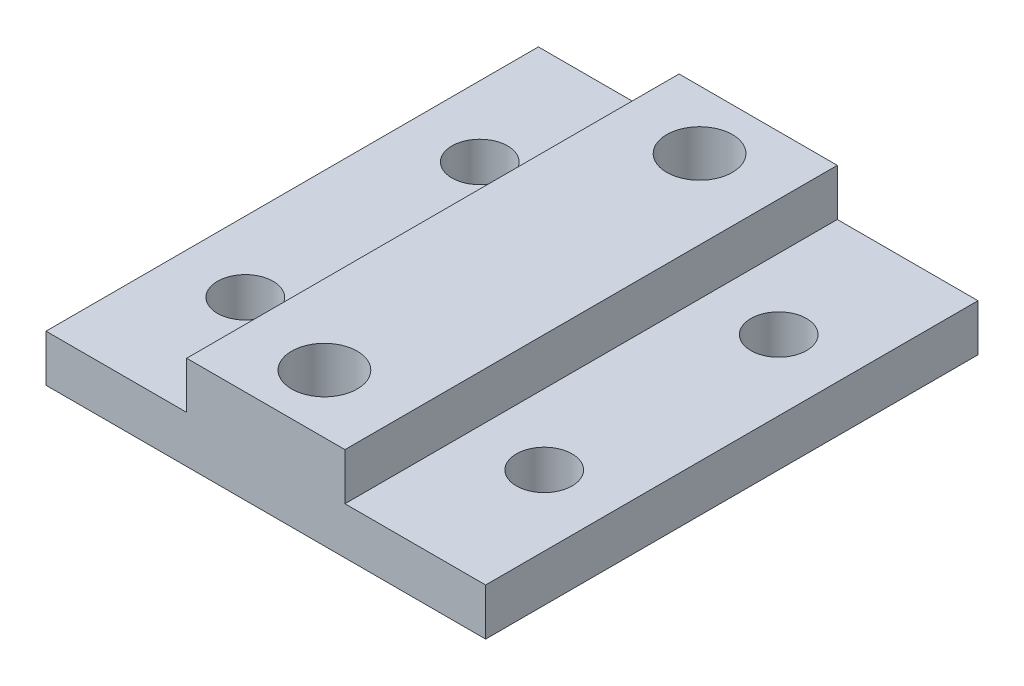
SolidWorks part; units mm, degrees
note: The reader was unsure of these and kept them because the rebuilt part matched: shared geometry of "Esboço1<3>".
ref_plane "Plano frontal" through (0, 0, 0) normal (0, 0, 1) x (1, 0, 0)
ref_plane "Plano superior" through (0, 0, 0) normal (0, 1, 0) x (1, 0, 0)
ref_plane "Plano direito" through (0, 0, 0) normal (1, 0, 0) x (0, 0, -1)
sketch "Esboço1" plane through (0, 0, 0) normal (0, 1, 0) x (1, 0, 0)
  line L1 (-18.75, 21) -> (18.75, 21)
  line L2 (-18.75, 21) -> (-18.75, -21)
  line L3 (-18.75, -21) -> (18.75, -21)
  line L4 (18.75, 21) -> (18.75, -21)
  line L5 (-18.75, 21) -> (18.75, -21) construction
  line L6 (-18.75, -21) -> (18.75, 21) construction
  line L7 (-6.75, -21) -> (6.75, -21)
  line L8 (-6.75, -21) -> (-6.75, 21)
  line L9 (-6.75, 21) -> (6.75, 21)
  line L10 (6.75, -21) -> (6.75, 21)
  line L11 (-6.75, -21) -> (6.75, 21) construction
  line L12 (-6.75, 21) -> (6.75, -21) construction
  circle A0 centre (0, 16) radius 2.8
  circle A1 centre (0, -16) radius 2.8
  circle A2 centre (12.75, 10) radius 2.375
  circle A3 centre (12.75, -10) radius 2.375
  circle A4 centre (-12.75, 10) radius 2.375
  circle A5 centre (-12.75, -10) radius 2.375
  point P0 (0, 0)
  point P18 (0, 0)
  dimension "D1" = 5.6
  dimension "D2" = 5.6
  dimension "D3" = 4.75
  dimension "D4" = 4.75
  dimension "D5" = 4.75
  dimension "D6" = 4.75
  dimension "D7" = 11
  dimension "D8" = 11
  dimension "D9" = 11
  dimension "D11" = 6
  dimension "D12" = 6
  dimension "D13" = 6
  dimension "D14" = 6
  dimension "D16" = 42
  dimension "D17" = 32
  dimension "D18" = 16
  dimension "D10" = 20
  dimension "D19" = 13.5
  dimension "D15" = 6
extrude "Ressalto-extrusão1" add sketch "Esboço1" along normal blind 5 contours L3 L8 L1 L2 A5 A4 | L3 L10 L1 L8 A1 A0 | L10 L3 L4 L1 A3 A2
sketch "Esboço2" plane through (0, 5, 0) normal (0, 1, 0) x (1, 0, 0)
  line L1 (5.0229, 16) -> (2.5115, 20.35)
  line L2 (2.5115, 20.35) -> (-2.5115, 20.35)
  line L3 (-2.5115, 20.35) -> (-5.0229, 16)
  line L4 (-5.0229, 16) -> (-2.5115, 11.65)
  line L5 (-2.5115, 11.65) -> (2.5115, 11.65)
  line L6 (2.5115, 11.65) -> (5.0229, 16)
  line L7 (5.0229, -16) -> (2.5115, -11.65)
  line L8 (2.5115, -11.65) -> (-2.5115, -11.65)
  line L9 (-2.5115, -11.65) -> (-5.0229, -16)
  line L10 (-5.0229, -16) -> (-2.5115, -20.35)
  line L11 (-2.5115, -20.35) -> (2.5115, -20.35)
  line L12 (2.5115, -20.35) -> (5.0229, -16)
  circle A0 centre (0, 16) radius 4.35 construction
  circle A1 centre (0, -16) radius 4.35 construction
  dimension "D1" = 8.7
  dimension "D2" = 8.7
extrude "Corte-extrusão1" cut sketch "Esboço2" along normal blind 4 from vertex
extrude "Ressalto-extrusão2" add sketch "Esboço1<3>" along normal blind 4 from vertex at 5 contours L3 L10 L1 L8 A1 A0 starting at point (-18.75, 5, 21)
sketch "Esboço1<3>" plane through (0, 0, 0) normal (0, 1, 0) x (1, 0, 0) same geometry as "Esboço1"
chamfer "Chanfro1" distance 1 angle 45 20 edges at (0, 0, 20.35) (-3.7672, 0, 18.175) (-3.7672, 0, 13.825) (0, 0, 11.65) (3.7672, 0, 13.825) (3.7672, 0, 18.175) (12.75, 0, -7.625) (12.75, 0, 12.375) (18.75, 0, 0) (0, 0, -21) (-18.75, 0, 0) (0, 0, 21) (-12.75, 0, -7.625) (-12.75, 0, 12.375) (0, 0, -11.65) (-3.7672, 0, -13.825) (-3.7672, 0, -18.175) (0, 0, -20.35) (3.7672, 0, -18.175) (3.7672, 0, -13.825)
equation "\"D2@Esboço1\"=\"D1@Esboço1\""
equation "\"D4@Esboço1\"=\"D3@Esboço1\""
equation "\"D5@Esboço1\"=\"D3@Esboço1\""
equation "\"D6@Esboço1\"=\"D3@Esboço1\""
equation "\"D13@Esboço1\"=\"D14@Esboço1\""
equation "\"D12@Esboço1\"=\"D14@Esboço1\""
equation "\"D11@Esboço1\"=\"D14@Esboço1\""
equation "\"D8@Esboço1\"=\"D7@Esboço1\""
equation "\"D9@Esboço1\"=\"D7@Esboço1\""
equation "\"D18@Esboço1\"=\"D17@Esboço1\"/2"
equation "\"D2@Esboço2\"=\"D1@Esboço2\""
